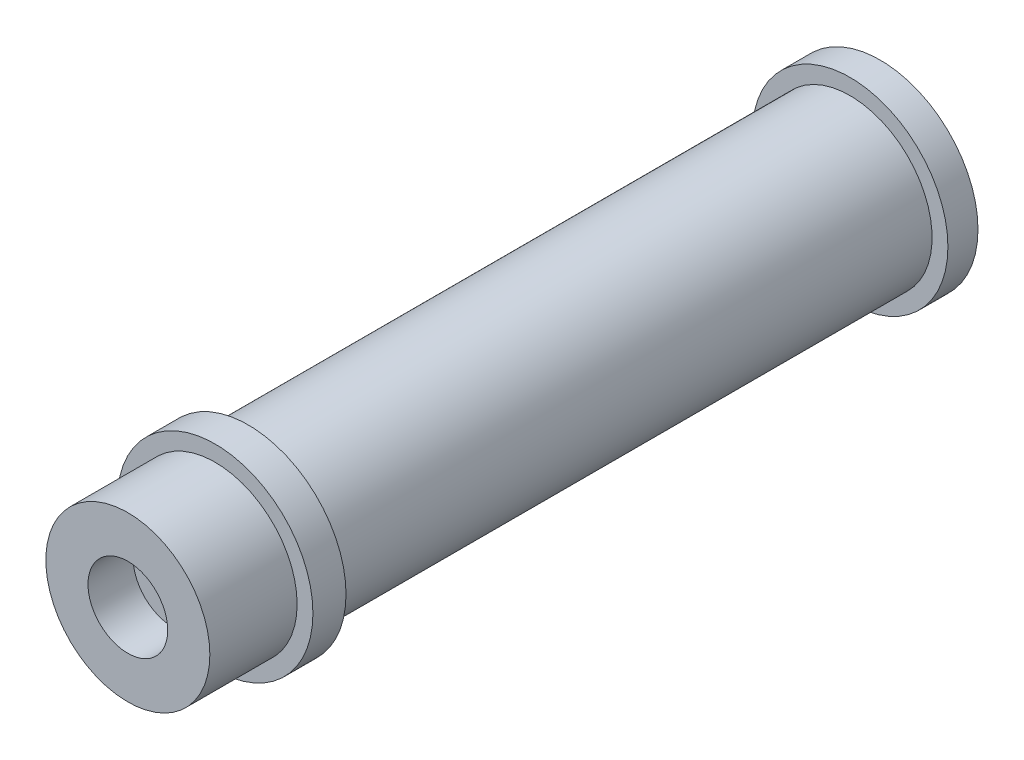
SolidWorks part; units mm, degrees
ref_plane "Front Plane" through (0, 0, 0) normal (0, 0, 1) x (1, 0, 0)
ref_plane "Top Plane" through (0, 0, 0) normal (0, 1, 0) x (1, 0, 0)
ref_plane "Right Plane" through (0, 0, 0) normal (1, 0, 0) x (0, 0, -1)
sketch "Sketch1" plane through (0, 0, 0) normal (0, 0, 1) x (1, 0, 0)
  line L0 (0, -6.5) -> (0, 6.5) construction
  circle A0 centre (0, 0) radius 6.5
  point P6 (0, 0)
  dimension "D2" = 13
extrude "Boss-Extrude1" add sketch "Sketch1" along normal blind 50
sketch "Sketch6" plane through (0, 0, 0) normal (0, 0, -1) x (-1, 0, 0)
  circle A0 centre (0, 0) radius 2.5
  dimension "D1" = 5
extrude "Boss-Extrude2" add sketch "Sketch6" along normal blind 2.5
sketch "Sketch7" plane through (0, 0, 50) normal (0, 0, 1) x (1, 0, 0)
  circle A0 centre (0, 0) radius 2.65
  dimension "D1" = 5.3
extrude "Cut-Extrude1" cut sketch "Sketch7" against normal blind 3
sketch "Sketch9" plane through (0, 0, 50) normal (0, 0, 1) x (1, 0, 0)
  circle A0 centre (0, 0) radius 5.45
  dimension "D1" = 10.9
extrude "Cut-Extrude2" cut sketch "Sketch9" against normal blind 5.8 flip side to cut contours A0
sketch "Sketch11" plane through (0, 0, 0) normal (0, 0, -1) x (-1, 0, 0)
  circle A0 centre (0, 0) radius 5.45
  dimension "D1" = 10.9
extrude "Cut-Extrude3" cut sketch "Sketch11" against normal blind 40 from offset 2 flip side to cut offset against normal yes
